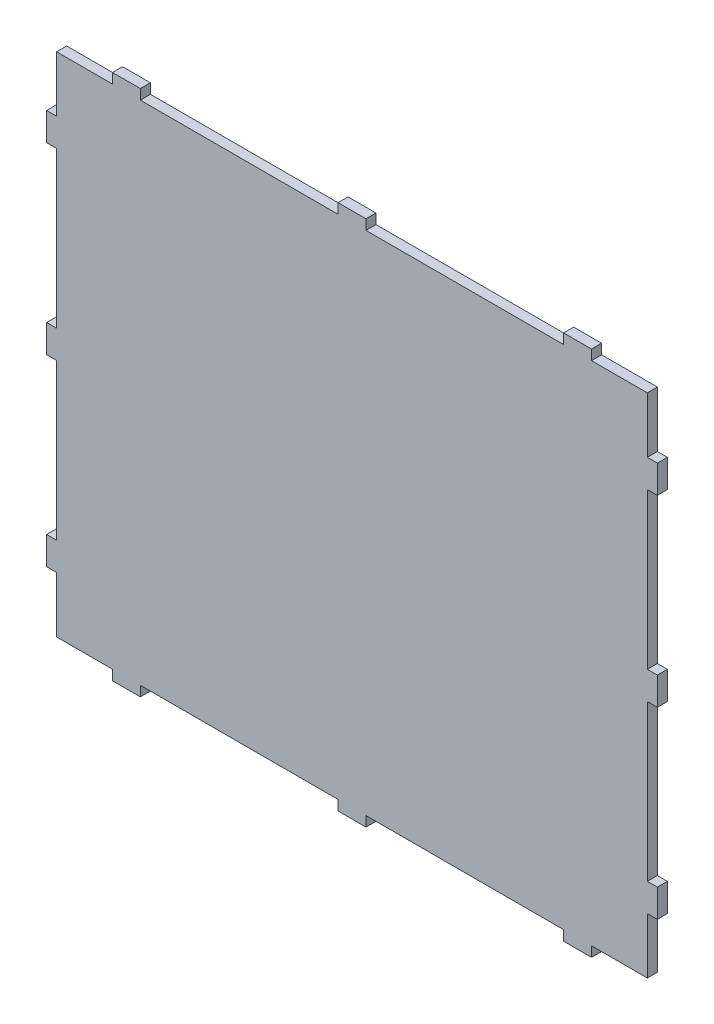
SolidWorks part; units mm, degrees
ref_plane "Front Plane" through (0, 0, 0) normal (0, 0, 1) x (1, 0, 0)
ref_plane "Top Plane" through (0, 0, 0) normal (0, 1, 0) x (1, 0, 0)
ref_plane "Right Plane" through (0, 0, 0) normal (1, 0, 0) x (0, 0, -1)
sketch "Sketch1" plane through (0, 0, 0) normal (0, 0, 1) x (1, 0, 0)
  line L0 (-961.2365, 328.9507) -> (-961.2365, 378.9507)
  line L8 (-943.2365, 807.9015) -> (-943.2365, 707.9015)
  line L9 (-943.2365, 707.9015) -> (-961.2365, 707.9015)
  line L10 (-961.2365, 657.9015) -> (-943.2365, 657.9015)
  line L11 (-943.2365, 657.9015) -> (-943.2365, 378.9507)
  line L12 (-943.2365, 378.9507) -> (-961.2365, 378.9507)
  line L13 (-961.2365, 657.9015) -> (-961.2365, 707.9015)
  line L18 (-414.1183, 825.9015) -> (-414.1183, 353.9507) construction
  line L19 (-961.2365, 353.9507) -> (-414.1183, 353.9507) construction
  line L20 (-943.2365, 807.9015) -> (-843.2365, 807.9015)
  line L21 (-843.2365, 807.9015) -> (-843.2365, 825.9015)
  line L22 (-843.2365, 825.9015) -> (-793.2365, 825.9015)
  line L23 (-793.2365, 825.9015) -> (-793.2365, 807.9015)
  line L24 (-793.2365, 807.9015) -> (-439.1183, 807.9015)
  line L25 (-439.1183, 807.9015) -> (-439.1183, 825.9015)
  line L26 (-843.2365, 603) -> (-843.2365, 0) construction
  line L28 (-439.1183, 825.9015) -> (-389.1183, 825.9015)
  line L29 (-788.166, 707.9015) -> (-779.041, 707.9015) construction
  line L30 (-439.1183, -118) -> (-389.1183, -118)
  line L31 (-439.1183, -100) -> (-439.1183, -118)
  line L32 (-793.2365, -100) -> (-439.1183, -100)
  line L33 (-793.2365, -118) -> (-793.2365, -100)
  line L34 (-843.2365, -118) -> (-793.2365, -118)
  line L35 (-843.2365, -100) -> (-843.2365, -118)
  line L36 (-943.2365, -100) -> (-843.2365, -100)
  line L37 (-961.2365, 50) -> (-961.2365, 0)
  line L38 (-943.2365, 328.9507) -> (-961.2365, 328.9507)
  line L39 (-943.2365, 50) -> (-943.2365, 328.9507)
  line L40 (-961.2365, 50) -> (-943.2365, 50)
  line L41 (-943.2365, 0) -> (-961.2365, 0)
  line L42 (-943.2365, -100) -> (-943.2365, 0)
  line L43 (-841.2365, 0) -> (-832.7445, 0) construction
  line L44 (115, -100) -> (115, 0)
  line L45 (115, 0) -> (133, 0)
  line L46 (133, 50) -> (115, 50)
  line L47 (115, 50) -> (115, 328.9507)
  line L48 (115, 328.9507) -> (133, 328.9507)
  line L49 (133, 50) -> (133, 0)
  line L50 (115, -100) -> (15, -100)
  line L51 (15, -100) -> (15, -118)
  line L52 (15, -118) -> (-35, -118)
  line L53 (-35, -118) -> (-35, -100)
  line L54 (-35, -100) -> (-389.1183, -100)
  line L55 (-389.1183, -100) -> (-389.1183, -118)
  line L56 (-389.1183, 807.9015) -> (-389.1183, 825.9015)
  line L57 (-35, 807.9015) -> (-389.1183, 807.9015)
  line L58 (-35, 825.9015) -> (-35, 807.9015)
  line L59 (15, 825.9015) -> (-35, 825.9015)
  line L60 (15, 807.9015) -> (15, 825.9015)
  line L61 (115, 807.9015) -> (15, 807.9015)
  line L62 (133, 657.9015) -> (133, 707.9015)
  line L63 (115, 378.9507) -> (133, 378.9507)
  line L64 (115, 657.9015) -> (115, 378.9507)
  line L65 (133, 657.9015) -> (115, 657.9015)
  line L66 (115, 707.9015) -> (133, 707.9015)
  line L67 (115, 807.9015) -> (115, 707.9015)
  line L68 (133, 328.9507) -> (133, 378.9507)
  line L69 (15, 603) -> (15, 0) construction
  point P24 (-961.2365, 353.9507)
  point P52 (-414.1183, -118)
  point P65 (133, 353.9507)
  dimension "D6" = 50
  dimension "D7" = 18
  dimension "D10" = 100
  dimension "D2" = 25
  dimension "D3" = 50
  dimension "D4" = 100
  dimension "D5" = 18
  dimension "D9" = 100
  dimension "D11" = 25
  dimension "D12" = 100
  dimension "D8" = 100
  dimension "D13" = 100
extrude "Boss-Extrude1" add sketch "Sketch1" along normal blind 18
sketch "Sketch2" plane through (0, 0, 0) normal (0, 0, -1) x (-1, 0, 0)
  line L0 (15, 30) -> (813.2365, 30)
  line L1 (813.2365, 30) -> (813.2365, 573)
  line L2 (813.2365, 573) -> (15, 573)
  line L3 (15, 573) -> (15, 30)
  line L4 (961.2365, 657.9015) -> (961.2365, 707.9015)
  line L5 (961.2365, 657.9015) -> (961.2365, 707.9015)
  line L6 (961.2365, 707.9015) -> (943.2365, 707.9015)
  line L7 (961.2365, 707.9015) -> (943.2365, 707.9015)
  line L64 (943.2365, 707.9015) -> (943.2365, 807.9015)
  line L65 (943.2365, 707.9015) -> (943.2365, 807.9015)
  line L66 (943.2365, 807.9015) -> (843.2365, 807.9015)
  line L67 (943.2365, 807.9015) -> (843.2365, 807.9015)
  line L68 (843.2365, 807.9015) -> (843.2365, 825.9015)
  line L69 (843.2365, 807.9015) -> (843.2365, 825.9015)
  line L70 (843.2365, 825.9015) -> (793.2365, 825.9015)
  line L71 (843.2365, 825.9015) -> (793.2365, 825.9015)
  line L72 (793.2365, 825.9015) -> (793.2365, 807.9015)
  line L73 (793.2365, 825.9015) -> (793.2365, 807.9015)
  line L74 (793.2365, 807.9015) -> (439.1183, 807.9015)
  line L75 (793.2365, 807.9015) -> (439.1183, 807.9015)
  line L76 (439.1183, 807.9015) -> (439.1183, 825.9015)
  line L77 (439.1183, 807.9015) -> (439.1183, 825.9015)
  line L78 (439.1183, 825.9015) -> (389.1183, 825.9015)
  line L79 (439.1183, 825.9015) -> (389.1183, 825.9015)
  line L80 (389.1183, 825.9015) -> (389.1183, 807.9015)
  line L81 (389.1183, 825.9015) -> (389.1183, 807.9015)
  line L82 (389.1183, 807.9015) -> (35, 807.9015)
  line L83 (389.1183, 807.9015) -> (35, 807.9015)
  line L84 (35, 807.9015) -> (35, 825.9015)
  line L85 (35, 807.9015) -> (35, 825.9015)
  line L86 (35, 825.9015) -> (-15, 825.9015)
  line L87 (35, 825.9015) -> (-15, 825.9015)
  line L88 (-15, 825.9015) -> (-15, 807.9015)
  line L89 (-15, 825.9015) -> (-15, 807.9015)
  line L90 (-15, 807.9015) -> (-115, 807.9015)
  line L91 (-15, 807.9015) -> (-115, 807.9015)
  line L92 (-115, 807.9015) -> (-115, 707.9015)
  line L93 (-115, 807.9015) -> (-115, 707.9015)
  line L94 (-115, 707.9015) -> (-133, 707.9015)
  line L95 (-115, 707.9015) -> (-133, 707.9015)
  line L96 (-133, 707.9015) -> (-133, 657.9015)
  line L97 (-133, 707.9015) -> (-133, 657.9015)
  line L98 (-133, 657.9015) -> (-115, 657.9015)
  line L99 (-133, 657.9015) -> (-115, 657.9015)
  line L100 (-115, 657.9015) -> (-115, 378.9507)
  line L101 (-115, 657.9015) -> (-115, 378.9507)
  line L102 (-115, 378.9507) -> (-133, 378.9507)
  line L103 (-115, 378.9507) -> (-133, 378.9507)
  line L104 (-133, 378.9507) -> (-133, 328.9507)
  line L105 (-133, 378.9507) -> (-133, 328.9507)
  line L106 (-133, 328.9507) -> (-115, 328.9507)
  line L107 (-133, 328.9507) -> (-115, 328.9507)
  line L108 (-115, 328.9507) -> (-115, 50)
  line L109 (-115, 328.9507) -> (-115, 50)
  line L110 (-115, 50) -> (-133, 50)
  line L111 (-115, 50) -> (-133, 50)
  line L112 (-133, 50) -> (-133, 0)
  line L113 (-133, 50) -> (-133, 0)
  line L114 (-133, 0) -> (-115, 0)
  line L115 (-133, 0) -> (-115, 0)
  line L116 (-115, 0) -> (-115, -100)
  line L117 (-115, 0) -> (-115, -100)
  line L118 (-115, -100) -> (-15, -100)
  line L119 (-115, -100) -> (-15, -100)
  line L120 (-15, -100) -> (-15, -118)
  line L121 (-15, -100) -> (-15, -118)
  line L122 (-15, -118) -> (35, -118)
  line L123 (-15, -118) -> (35, -118)
  line L124 (35, -118) -> (35, -100)
  line L125 (35, -118) -> (35, -100)
  line L126 (35, -100) -> (389.1183, -100)
  line L127 (35, -100) -> (389.1183, -100)
  line L128 (389.1183, -100) -> (389.1183, -118)
  line L129 (389.1183, -100) -> (389.1183, -118)
  line L130 (389.1183, -118) -> (439.1183, -118)
  line L131 (389.1183, -118) -> (439.1183, -118)
  line L132 (439.1183, -118) -> (439.1183, -100)
  line L133 (439.1183, -118) -> (439.1183, -100)
  line L134 (439.1183, -100) -> (793.2365, -100)
  line L135 (439.1183, -100) -> (793.2365, -100)
  line L136 (793.2365, -100) -> (793.2365, -118)
  line L137 (793.2365, -100) -> (793.2365, -118)
  line L138 (793.2365, -118) -> (843.2365, -118)
  line L139 (793.2365, -118) -> (843.2365, -118)
  line L140 (843.2365, -118) -> (843.2365, -100)
  line L141 (843.2365, -118) -> (843.2365, -100)
  line L142 (843.2365, -100) -> (943.2365, -100)
  line L143 (843.2365, -100) -> (943.2365, -100)
  line L144 (943.2365, -100) -> (943.2365, 0)
  line L145 (943.2365, -100) -> (943.2365, 0)
  line L146 (943.2365, 0) -> (961.2365, 0)
  line L147 (943.2365, 0) -> (961.2365, 0)
  line L148 (961.2365, 0) -> (961.2365, 50)
  line L149 (961.2365, 0) -> (961.2365, 50)
  line L150 (961.2365, 50) -> (943.2365, 50)
  line L151 (961.2365, 50) -> (943.2365, 50)
  line L152 (943.2365, 50) -> (943.2365, 328.9507)
  line L153 (943.2365, 50) -> (943.2365, 328.9507)
  line L154 (943.2365, 328.9507) -> (961.2365, 328.9507)
  line L155 (943.2365, 328.9507) -> (961.2365, 328.9507)
  line L156 (961.2365, 328.9507) -> (961.2365, 378.9507)
  line L157 (961.2365, 328.9507) -> (961.2365, 378.9507)
  line L158 (961.2365, 378.9507) -> (943.2365, 378.9507)
  line L159 (961.2365, 378.9507) -> (943.2365, 378.9507)
  line L160 (943.2365, 378.9507) -> (943.2365, 657.9015)
  line L161 (943.2365, 378.9507) -> (943.2365, 657.9015)
  line L162 (943.2365, 657.9015) -> (961.2365, 657.9015)
  line L163 (943.2365, 657.9015) -> (961.2365, 657.9015)
  dimension "D1" = 0
extrude "Cut-Extrude1" [suppressed] cut sketch "Sketch2" against normal through all flip side to cut
sketch "Sketch3" [suppressed] plane through (0, 0, 0) normal (0, 0, -1) x (-1, 0, 0)
  line L0 (15, 603) -> (15, 0) construction
  line L1 (813.2365, 573) -> (15, 573)
  line L2 (813.2365, 573) -> (813.2365, 562.1515)
  line L3 (813.2365, 562.1515) -> (15, 562.1515)
  line L4 (15, 573) -> (15, 562.1515)
  line L5 (215.9071, 592.1515) -> (206.7821, 592.1515) construction
  dimension "D1" = 30
extrude "Boss-Extrude2" [suppressed] add sketch "Sketch3" against normal up to surface (18 mm away) up to face at (-414.1183, 353.9507, 18)
equation "\"fingerlenght\"=50"
equation "\"D6@Sketch1\"=\"fingerlenght\""
equation "\"fingerendclearance\"=100"
equation "\"osbthickness\"=18"
equation "\"D7@Sketch1\"=\"osbthickness\""
equation "\"D2@Sketch1\"=\"fingerlenght\"/2"
equation "\"D3@Sketch1\"=\"fingerlenght\""
equation "\"D4@Sketch1\"=\"fingerendclearance\""
equation "\"D5@Sketch1\"=\"osbthickness\""
equation "\"D9@Sketch1\"=\"fingerendclearance\""
equation "\"D11@Sketch1\"=\"fingerlenght\"/2"
equation "\"wallclearance\"=100"
equation "\"D12@Sketch1\"=\"wallclearance\""
equation "\"D10@Sketch1\"=\"wallclearance\""
equation "\"D13@Sketch1\"=\"wallclearance\""
